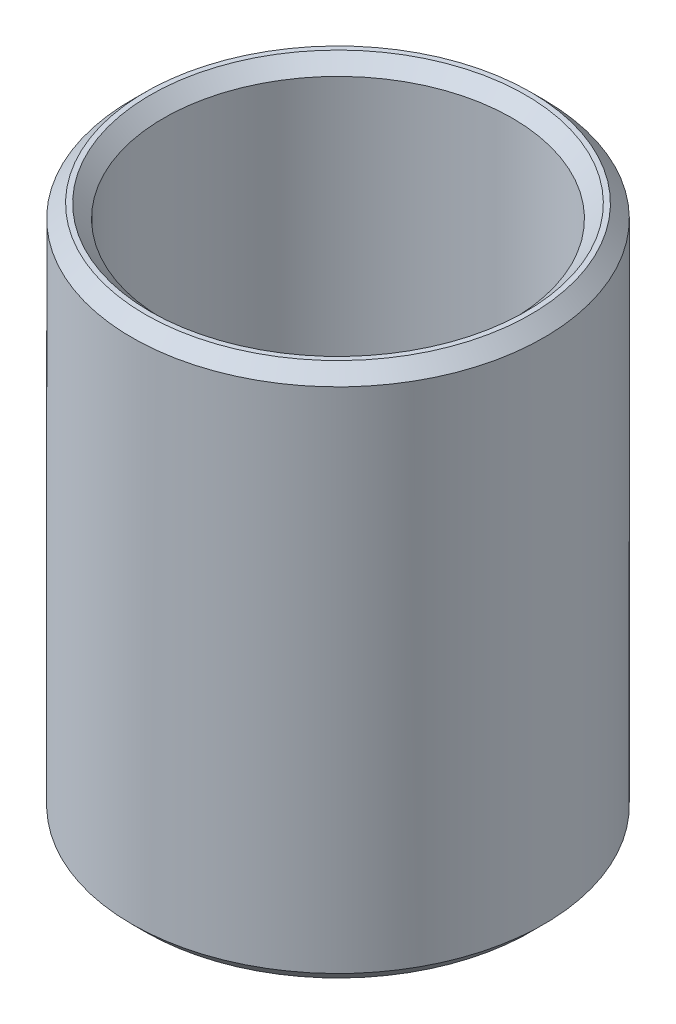
SolidWorks part; units mm, degrees
ref_plane "Front Plane" through (0, 0, 0) normal (0, 0, 1) x (1, 0, 0)
ref_plane "Top Plane" through (0, 0, 0) normal (0, 1, 0) x (1, 0, 0)
ref_plane "Right Plane" through (0, 0, 0) normal (1, 0, 0) x (0, 0, -1)
sketch "Sketch1" plane through (0, 0, 0) normal (0, 1, 0) x (1, 0, 0)
  circle A0 centre (0, 0) radius 60
  dimension "SLEEVE_OD" = 120
extrude "Boss-Extrude1" add sketch "Sketch1" along normal blind 155.7399
sketch "Sketch2" plane through (0, 0, 0) normal (0, 1, 0) x (1, 0, 0)
  circle A0 centre (0, 0) radius 50.7647
  dimension "BORE_D" = 101.5294
extrude "Cut-Extrude1" cut sketch "Sketch2" along normal through all
chamfer "Chamfer1" distance 3.8876 angle 45 4 edges at (0, 155.7399, 50.7647) (0, 0, 50.7647) (0, 0, 60) (0, 155.7399, 60)
